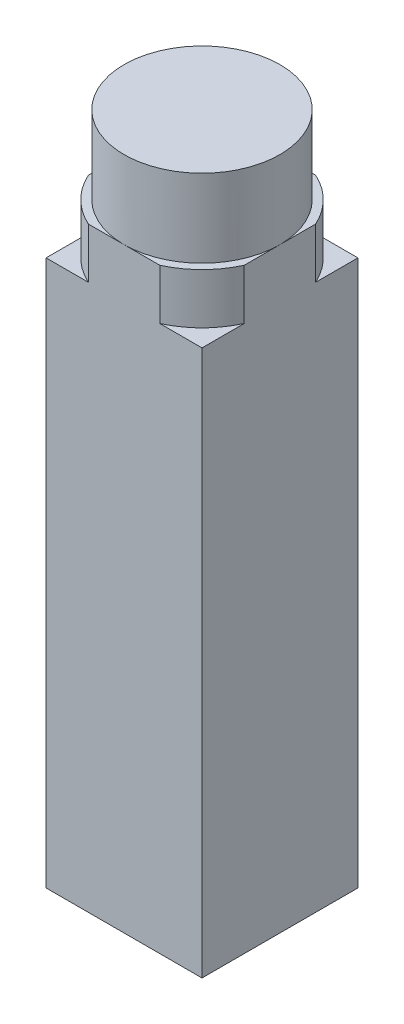
SolidWorks part; units mm, degrees
ref_plane "Front Plane" through (0, 0, 0) normal (0, 0, 1) x (1, 0, 0)
ref_plane "Top Plane" through (0, 0, 0) normal (0, 1, 0) x (1, 0, 0)
ref_plane "Right Plane" through (0, 0, 0) normal (1, 0, 0) x (0, 0, -1)
other "Configuration Table"
sketch "Sketch1" plane through (0, 0, 0) normal (0, 1, 0) x (1, 0, 0)
  line L1 (-3.175, 3.175) -> (3.175, 3.175)
  line L2 (-3.175, 3.175) -> (-3.175, -3.175)
  line L3 (-3.175, -3.175) -> (3.175, -3.175)
  line L4 (3.175, 3.175) -> (3.175, -3.175)
  line L5 (-3.175, 3.175) -> (3.175, -3.175) construction
  line L6 (-3.175, -3.175) -> (3.175, 3.175) construction
  point P0 (0, 0)
  dimension "D1" = 6.35
extrude "Boss-Extrude1" add sketch "Sketch1" along normal blind 22.225
sketch "Sketch2" plane through (0, 0, 0) normal (0, -1, 0) x (1, 0, 0)
  line L0 (3.175, 3.175) -> (3.175, -3.175) construction
  circle A0 centre (0, 0) radius 3.175
extrude "Boss-Extrude2" add sketch "Sketch2" against normal blind 27.4549
ref_plane "Plane1" through (0, 24.2799, 0) normal (0, 1, 0) x (1, 0, 0)
sketch "Sketch4" plane through (0, 24.2799, 0) normal (0, 1, 0) x (1, 0, 0)
  line L0 (-3.175, 0) -> (-3.175, -3.175) construction
  line L1 (0, -3.175) -> (3.175, -3.175) construction
  line L2 (-3.175, -3.175) -> (0, -3.175) construction
  line L3 (3.175, -3.175) -> (3.175, 0) construction
  line L4 (3.175, 0) -> (3.175, 3.175) construction
  line L5 (3.175, 3.175) -> (0, 3.175) construction
  line L6 (0, 3.175) -> (-3.175, 3.175) construction
  line L7 (-3.175, 3.175) -> (-3.175, 0) construction
  line L8 (-3.175, 0) -> (-3.175, -1.455)
  line L9 (0, -3.175) -> (1.455, -3.175)
  line L10 (-1.455, -3.175) -> (0, -3.175)
  line L11 (3.175, -1.455) -> (3.175, 0)
  line L12 (3.175, 0) -> (3.175, 1.455)
  line L13 (1.455, 3.175) -> (0, 3.175)
  line L14 (0, 3.175) -> (-1.455, 3.175)
  line L15 (-3.175, 1.455) -> (-3.175, 0)
  arc A0 (-3.175, -1.455) -> (-1.455, -3.175) centre (0, 0) ccw
  arc A1 (-1.455, 3.175) -> (-3.175, 1.455) centre (0, 0) ccw
  arc A2 (3.175, 1.455) -> (1.455, 3.175) centre (0, 0) ccw
  arc A3 (1.455, -3.175) -> (3.175, -1.455) centre (0, 0) ccw
  dimension "D1" = 6.985
extrude "Boss-Extrude3" add sketch "Sketch4" against normal up to surface (2.0549 mm away) up to face at (-2.3359, 22.225, 2.3359)
sketch "Sketch5" plane through (0, 0, 0) normal (0, -1, 0) x (1, 0, 0)
  circle A0 centre (0, 0) radius 1.9844
  dimension "D1" = 3.9688
extrude "Cut-Extrude1" cut sketch "Sketch5" against normal blind 12.7
